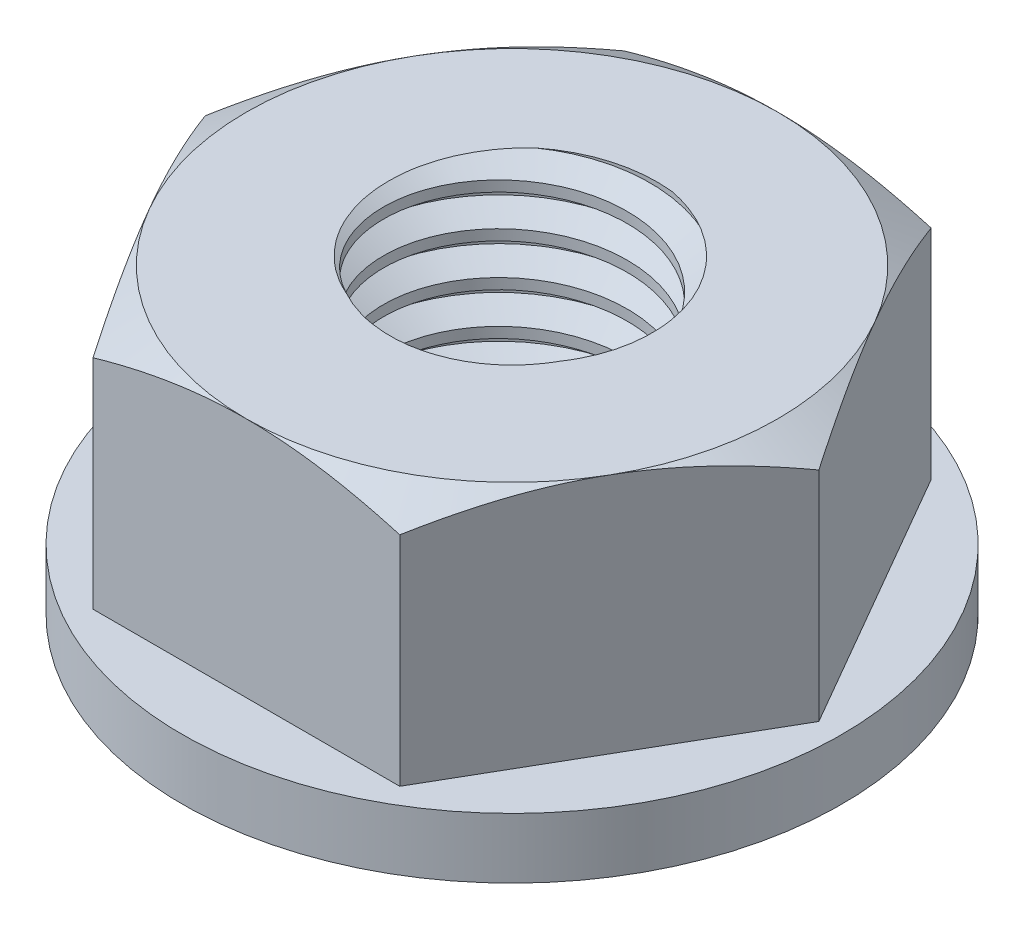
SolidWorks part; units mm, degrees
ref_plane "Front Plane" through (0, 0, 0) normal (0, 0, 1) x (1, 0, 0)
ref_plane "Top Plane" through (0, 0, 0) normal (0, 1, 0) x (1, 0, 0)
ref_plane "Right Plane" through (0, 0, 0) normal (1, 0, 0) x (0, 0, -1)
sketch "Sketch1" plane through (0, 0, 0) normal (0, 1, 0) x (1, 0, 0)
  line L1 (12.7017, 0) -> (6.3509, 11)
  line L2 (6.3509, 11) -> (-6.3509, 11)
  line L3 (-6.3509, 11) -> (-12.7017, 0)
  line L4 (-12.7017, 0) -> (-6.3509, -11)
  line L5 (-6.3509, -11) -> (6.3509, -11)
  line L6 (6.3509, -11) -> (12.7017, 0)
  circle A0 centre (0, 0) radius 11 construction
  dimension "D1" = 22
extrude "Boss-Extrude1" add sketch "Sketch1" along normal blind 10
sketch "Sketch2" plane through (0, 10, 0) normal (0, 1, 0) x (1, 0, 0)
  circle A0 centre (0, 0) radius 6
extrude "Cut-Extrude1" cut sketch "Sketch2" against normal through all
sketch "Sketch3" plane through (0, 10, 0) normal (0, 1, 0) x (1, 0, 0)
  circle A0 centre (0, 0) radius 11
extrude "Cut-Extrude2" cut sketch "Sketch3" against normal blind 10 draft 60 flip side to cut
thread "Thread2" pitch 1.75 method extrude profile "Thread Profile2" start angle 0, offset 2, length 0, pitch 1.75, diameter 12
ref_plane "Plane2" through (-6, 12, 0) normal (0, 0, 1) x (-1, 0, 0)
sketch "Thread Profile2" plane through (-6, 12, 0) normal (0, 0, 1) x (-1, 0, 0)
  line L0 (0, 0) -> (0, 1.75) construction
  line L11 (0, 0) -> (0, 1.5312)
  line L12 (0, 1.5312) -> (-0.9472, 0.9844)
  line L13 (-0.9472, 0.9844) -> (-0.9472, 0.5469)
  line L15 (-0.9472, 0.5469) -> (0, 0)
  line L17 (-0.9472, 0.7656) -> (0, 0.7656) construction
  point P2 (0, 0)
  dimension "Pitch" = 1.75
  dimension "Profile_Angle" = 60
  dimension "Profile_Land" = 0.4375
  dimension "Profile_Height" = 0.9472
sketch "Sketch12" plane through (0, 0, 11) normal (0, 0, 1) x (1, 0, 0)
  line L0 (-9.5263, 10) -> (-11, 10) construction
  line L1 (-11, 10) -> (11.3463, 10)
  line L2 (-11, 10) -> (-11, 12.7582)
  line L3 (-11, 12.7582) -> (11.3463, 12.7582)
  line L4 (11.3463, 10) -> (11.3463, 12.7582)
  line L5 (-12.7017, 0) -> (-6.3509, 0) construction
  line L6 (-11, 0) -> (12.6345, 0)
  line L7 (-11, 0) -> (-11, -3.2207)
  line L8 (-11, -3.2207) -> (12.6345, -3.2207)
  line L9 (12.6345, 0) -> (12.6345, -3.2207)
extrude "Cut-Extrude3" cut sketch "Sketch12" against normal through all
sketch "Sketch13" plane through (0, 0, 0) normal (0, -1, 0) x (1, 0, 0)
  circle A0 centre (0, 0) radius 13.6452
extrude "Boss-Extrude2" add sketch "Sketch13" along normal blind 2.5
sketch "Sketch14" plane through (0, 10, 0) normal (0, 1, 0) x (1, 0, 0)
  circle A0 centre (0, 0) radius 5
extrude "Cut-Extrude4" cut sketch "Sketch14" against normal through all
